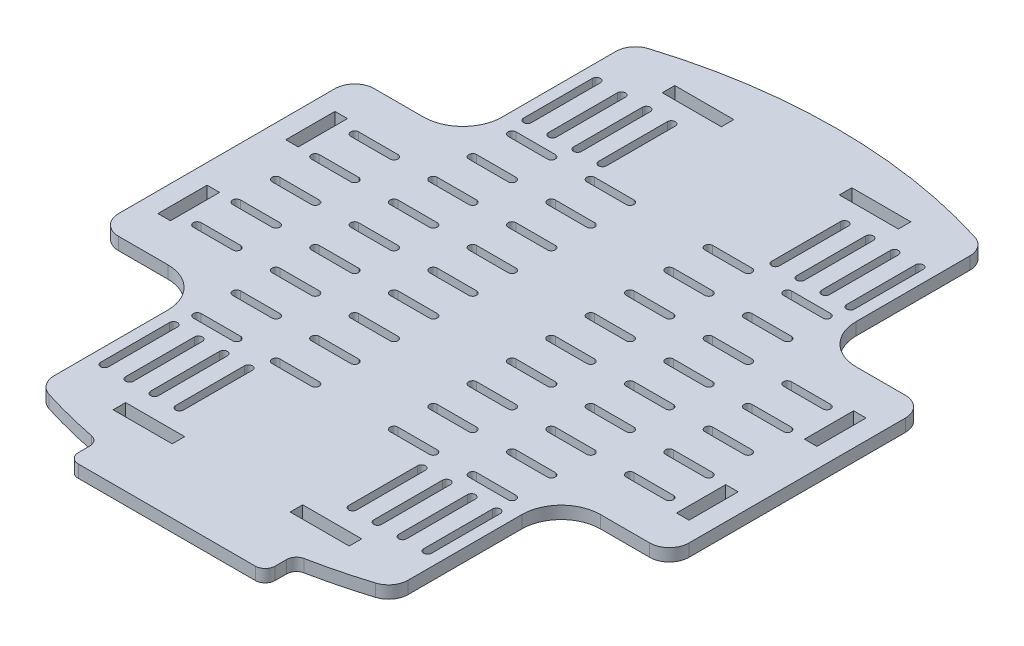
SolidWorks part; units mm, degrees
ref_plane "Plan de face" through (0, 0, 0) normal (0, 0, 1) x (1, 0, 0)
ref_plane "Plan de dessus" through (0, 0, 0) normal (0, 1, 0) x (1, 0, 0)
ref_plane "Plan de droite" through (0, 0, 0) normal (1, 0, 0) x (0, 0, -1)
sketch "Esquisse1" plane through (0, 0, 0) normal (0, 1, 0) x (1, 0, 0)
  line L0 (-145, 0) -> (0, 0) construction
  line L1 (-90, -150) -> (90, -150)
  line L2 (-90, -150) -> (-90, 150)
  line L3 (-90, 150) -> (90, 150)
  line L4 (90, -150) -> (90, 150)
  line L5 (-90, -150) -> (90, 150) construction
  line L6 (-90, 150) -> (90, -150) construction
  line L7 (-90, 65) -> (-145, 65)
  line L8 (-90, 65) -> (-90, -65)
  line L9 (-90, -65) -> (-145, -65)
  line L10 (-145, 65) -> (-145, -65)
  line L11 (0, 0) -> (0, -275) construction
  line L12 (90, -65) -> (145, -65)
  line L13 (145, 65) -> (145, -65)
  line L14 (90, 65) -> (145, 65)
  line L15 (90, 65) -> (90, -65)
  arc A0 (-90, 150) -> (90, 150) centre (0, -112.5) cw
  arc A1 (-90, -150) -> (90, -150) centre (0, 112.5) ccw
  point P0 (0, 0)
  point P19 (0, 165)
  point P20 (0, -165)
  dimension "D1" = 180
  dimension "D2" = 300
  dimension "D3" = 85
  dimension "D4" = 55
  dimension "D5" = 15
  dimension "D6" = 15
extrude "Boss.-Extru.1" add sketch "Esquisse1" along normal blind 6.35 contours L1 L4 L3 L2 | L7 L10 L9 L2 | L14 L4 L12 L13 | L1 A1 | A0 L3 region at (0, 0, 0) region at (0, 0, 156.0141) region at (-117.5, 0, 0) region at (117.5, 0, 0) region at (0, 0, -156.0141)
ref_plane "Plan1" through (0, 0, 150) normal (0, 0, -1) x (-1, 0, 0)
ref_plane "Plan3" through (0, 0, -150) normal (0, 0, -1) x (-1, 0, 0)
ref_plane "Wheel axis1" through (0, 0, 107.5) normal (0, 0, 1) x (1, 0, 0)
ref_plane "Wheel axis2" through (0, 0, -107.5) normal (0, 0, -1) x (-1, 0, 0)
sketch "Esquisse3" plane through (0, 6.35, 0) normal (0, 1, 0) x (1, 0, 0)
  line L0 (0, -160.4583) -> (0, 0) construction
  line L1 (-50, -160.4583) -> (50, -160.4583)
  line L2 (-50, -160.4583) -> (-50, -175.4583)
  line L3 (-50, -175.4583) -> (50, -175.4583)
  line L4 (50, -160.4583) -> (50, -175.4583)
  arc A0 (-90, -150) -> (90, -150) centre (0, 112.5) ccw construction
  dimension "D1" = 15
  dimension "D2" = 100
extrude "Boss.-Extru.2" add sketch "Esquisse3" against normal up to surface (6.35 mm away) up to face at (0, 0, 0)
sketch "Esquisse2" plane through (0, 0, 0) normal (0, -1, 0) x (1, 0, 0)
  line L0 (-128.65, 45) -> (-135, 45) construction
  line L1 (-135, 45) -> (-135, 20) construction
  line L2 (-135, 20) -> (-128.65, 20) construction
  line L3 (-128.65, 20) -> (-128.65, 45) construction
  line L4 (-128.65, -20) -> (-135, -20) construction
  line L5 (-135, -20) -> (-135, -45) construction
  line L6 (-135, -45) -> (-128.65, -45) construction
  line L7 (-128.65, -45) -> (-128.65, -20) construction
  line L8 (-60, -136.4072) -> (-60, -142.7572) construction
  line L9 (-60, -142.7572) -> (-30, -142.7572) construction
  line L10 (-30, -142.7572) -> (-30, -136.4072) construction
  line L11 (-30, -136.4072) -> (-60, -136.4072) construction
  line L12 (30, -136.4072) -> (30, -142.7572) construction
  line L13 (30, -142.7572) -> (60, -142.7572) construction
  line L14 (60, -142.7572) -> (60, -136.4072) construction
  line L15 (60, -136.4072) -> (30, -136.4072) construction
  line L16 (135, -20) -> (128.65, -20) construction
  line L17 (128.65, -20) -> (128.65, -45) construction
  line L18 (128.65, -45) -> (135, -45) construction
  line L19 (135, -45) -> (135, -20) construction
  line L20 (135, 45) -> (128.65, 45) construction
  line L21 (128.65, 45) -> (128.65, 20) construction
  line L22 (128.65, 20) -> (135, 20) construction
  line L23 (135, 20) -> (135, 45) construction
  line L24 (30, 142.7572) -> (30, 136.4072) construction
  line L25 (30, 136.4072) -> (60, 136.4072) construction
  line L26 (60, 136.4072) -> (60, 142.7572) construction
  line L27 (60, 142.7572) -> (30, 142.7572) construction
  line L28 (-60, 142.7572) -> (-60, 136.4072) construction
  line L29 (-60, 136.4072) -> (-30, 136.4072) construction
  line L30 (-30, 136.4072) -> (-30, 142.7572) construction
  line L31 (-30, 142.7572) -> (-60, 142.7572) construction
  line L32 (-128.65, 45) -> (-135, 45)
  line L33 (-135, 45) -> (-135, 20)
  line L34 (-135, 20) -> (-128.65, 20)
  line L35 (-128.65, 20) -> (-128.65, 45)
  line L36 (-128.65, -20) -> (-135, -20)
  line L37 (-135, -20) -> (-135, -45)
  line L38 (-135, -45) -> (-128.65, -45)
  line L39 (-128.65, -45) -> (-128.65, -20)
  line L40 (-60, -136.4072) -> (-60, -142.7572)
  line L41 (-60, -142.7572) -> (-30, -142.7572)
  line L42 (-30, -142.7572) -> (-30, -136.4072)
  line L43 (-30, -136.4072) -> (-60, -136.4072)
  line L44 (30, -136.4072) -> (30, -142.7572)
  line L45 (30, -142.7572) -> (60, -142.7572)
  line L46 (60, -142.7572) -> (60, -136.4072)
  line L47 (60, -136.4072) -> (30, -136.4072)
  line L48 (135, -20) -> (128.65, -20)
  line L49 (128.65, -20) -> (128.65, -45)
  line L50 (128.65, -45) -> (135, -45)
  line L51 (135, -45) -> (135, -20)
  line L52 (135, 45) -> (128.65, 45)
  line L53 (128.65, 45) -> (128.65, 20)
  line L54 (128.65, 20) -> (135, 20)
  line L55 (135, 20) -> (135, 45)
  line L56 (30, 142.7572) -> (30, 136.4072)
  line L57 (30, 136.4072) -> (60, 136.4072)
  line L58 (60, 136.4072) -> (60, 142.7572)
  line L59 (60, 142.7572) -> (30, 142.7572)
  line L60 (-60, 142.7572) -> (-60, 136.4072)
  line L61 (-60, 136.4072) -> (-30, 136.4072)
  line L62 (-30, 136.4072) -> (-30, 142.7572)
  line L63 (-30, 142.7572) -> (-60, 142.7572)
extrude "Enlèv. mat.-Extru.1" cut sketch "Esquisse2" against normal up to next
sketch "Esquisse4" plane through (0, 6.35, 0) normal (0, 1, 0) x (1, 0, 0)
  line L0 (-80, 0) -> (-60, 0) construction
  line L1 (-80, 2) -> (-60, 2)
  line L2 (-80, -2) -> (-60, -2)
  line L3 (-20, 0) -> (-40, 0) construction
  line L4 (-20, -2) -> (-40, -2)
  line L5 (-20, 2) -> (-40, 2)
  line L6 (30, 0) -> (-30, 0) construction
  line L7 (-30, 0) -> (-70, 0) construction
  line L8 (-80, 20) -> (-60, 20) construction
  line L9 (-80, 22) -> (-60, 22)
  line L10 (-80, 18) -> (-60, 18)
  line L11 (-20, 20) -> (-40, 20) construction
  line L12 (-20, 18) -> (-40, 18)
  line L13 (-20, 22) -> (-40, 22)
  line L14 (-80, 40) -> (-60, 40) construction
  line L15 (-80, 42) -> (-60, 42)
  line L16 (-80, 38) -> (-60, 38)
  line L17 (-20, 40) -> (-40, 40) construction
  line L18 (-20, 38) -> (-40, 38)
  line L19 (-20, 42) -> (-40, 42)
  line L20 (-80, 60) -> (-60, 60) construction
  line L21 (-80, 62) -> (-60, 62)
  line L22 (-80, 58) -> (-60, 58)
  line L23 (-20, 60) -> (-40, 60) construction
  line L24 (-20, 58) -> (-40, 58)
  line L25 (-20, 62) -> (-40, 62)
  line L26 (-80, -20) -> (-60, -20) construction
  line L27 (-80, -18) -> (-60, -18)
  line L28 (-80, -22) -> (-60, -22)
  line L29 (-20, -20) -> (-40, -20) construction
  line L30 (-20, -22) -> (-40, -22)
  line L31 (-20, -18) -> (-40, -18)
  line L32 (-80, -40) -> (-60, -40) construction
  line L33 (-80, -38) -> (-60, -38)
  line L34 (-80, -42) -> (-60, -42)
  line L35 (-20, -40) -> (-40, -40) construction
  line L36 (-20, -42) -> (-40, -42)
  line L37 (-20, -38) -> (-40, -38)
  line L38 (-80, -60) -> (-60, -60) construction
  line L39 (-80, -58) -> (-60, -58)
  line L40 (-80, -62) -> (-60, -62)
  line L41 (-20, -60) -> (-40, -60) construction
  line L42 (-20, -62) -> (-40, -62)
  line L43 (-20, -58) -> (-40, -58)
  line L44 (-80, -80) -> (-60, -80) construction
  line L45 (-80, -78) -> (-60, -78)
  line L46 (-80, -82) -> (-60, -82)
  line L47 (-20, -80) -> (-40, -80) construction
  line L48 (-20, -82) -> (-40, -82)
  line L49 (-20, -78) -> (-40, -78)
  line L50 (-120, 0) -> (-100, 0) construction
  line L53 (-120, 2) -> (-100, 2)
  line L56 (-120, -2) -> (-100, -2)
  line L59 (-120, 20) -> (-100, 20) construction
  line L62 (-80, 80) -> (-60, 80) construction
  line L63 (-80, 82) -> (-60, 82)
  line L64 (-80, 78) -> (-60, 78)
  line L65 (-20, 80) -> (-40, 80) construction
  line L66 (-20, 78) -> (-40, 78)
  line L67 (-20, 82) -> (-40, 82)
  line L68 (-120, 22) -> (-100, 22)
  line L71 (-120, 18) -> (-100, 18)
  line L74 (-120, 40) -> (-100, 40) construction
  line L77 (-120, 42) -> (-100, 42)
  line L80 (0, 0) -> (0, -28.7119) construction
  line L81 (80, 0) -> (60, 0) construction
  line L82 (80, 2) -> (60, 2)
  line L83 (80, -2) -> (60, -2)
  line L84 (20, 0) -> (40, 0) construction
  line L85 (20, -2) -> (40, -2)
  line L86 (20, 2) -> (40, 2)
  line L87 (80, 20) -> (60, 20) construction
  line L88 (80, 22) -> (60, 22)
  line L89 (80, 18) -> (60, 18)
  line L90 (20, 20) -> (40, 20) construction
  line L91 (20, 18) -> (40, 18)
  line L92 (20, 22) -> (40, 22)
  line L93 (80, 40) -> (60, 40) construction
  line L94 (80, 42) -> (60, 42)
  line L95 (80, 38) -> (60, 38)
  line L96 (20, 40) -> (40, 40) construction
  line L97 (20, 38) -> (40, 38)
  line L98 (20, 42) -> (40, 42)
  line L99 (80, 60) -> (60, 60) construction
  line L100 (80, 62) -> (60, 62)
  line L101 (80, 58) -> (60, 58)
  line L102 (20, 60) -> (40, 60) construction
  line L103 (20, 58) -> (40, 58)
  line L104 (20, 62) -> (40, 62)
  line L105 (80, -20) -> (60, -20) construction
  line L106 (80, -18) -> (60, -18)
  line L107 (80, -22) -> (60, -22)
  line L108 (20, -20) -> (40, -20) construction
  line L109 (20, -22) -> (40, -22)
  line L110 (20, -18) -> (40, -18)
  line L111 (80, -40) -> (60, -40) construction
  line L112 (80, -38) -> (60, -38)
  line L113 (80, -42) -> (60, -42)
  line L114 (20, -40) -> (40, -40) construction
  line L115 (20, -42) -> (40, -42)
  line L116 (20, -38) -> (40, -38)
  line L117 (80, -60) -> (60, -60) construction
  line L118 (80, -58) -> (60, -58)
  line L119 (80, -62) -> (60, -62)
  line L120 (20, -60) -> (40, -60) construction
  line L121 (20, -62) -> (40, -62)
  line L122 (20, -58) -> (40, -58)
  line L123 (80, -80) -> (60, -80) construction
  line L124 (80, -78) -> (60, -78)
  line L125 (80, -82) -> (60, -82)
  line L126 (20, -80) -> (40, -80) construction
  line L127 (20, -82) -> (40, -82)
  line L128 (20, -78) -> (40, -78)
  line L129 (-120, 38) -> (-100, 38)
  line L132 (-120, -20) -> (-100, -20) construction
  line L135 (-120, -18) -> (-100, -18)
  line L138 (-120, -22) -> (-100, -22)
  line L141 (80, 80) -> (60, 80) construction
  line L142 (80, 82) -> (60, 82)
  line L143 (80, 78) -> (60, 78)
  line L144 (20, 80) -> (40, 80) construction
  line L145 (20, 78) -> (40, 78)
  line L146 (20, 82) -> (40, 82)
  line L147 (-120, -40) -> (-100, -40) construction
  line L150 (-120, -38) -> (-100, -38)
  line L153 (-120, -42) -> (-100, -42)
  line L156 (120, 0) -> (100, 0) construction
  line L159 (30, 0) -> (70, 0) construction
  line L160 (120, 2) -> (100, 2)
  line L161 (120, -2) -> (100, -2)
  line L162 (120, 20) -> (100, 20) construction
  line L163 (120, 22) -> (100, 22)
  line L164 (120, 18) -> (100, 18)
  line L165 (120, 40) -> (100, 40) construction
  line L166 (120, 42) -> (100, 42)
  line L167 (120, 38) -> (100, 38)
  line L168 (120, -20) -> (100, -20) construction
  line L169 (120, -18) -> (100, -18)
  line L170 (120, -22) -> (100, -22)
  line L171 (120, -40) -> (100, -40) construction
  line L172 (120, -38) -> (100, -38)
  line L173 (120, -42) -> (100, -42)
  arc A0 (-80, 2) -> (-80, -2) centre (-80, 0) ccw
  arc A1 (-60, -2) -> (-60, 2) centre (-60, 0) ccw
  arc A2 (-20, -2) -> (-20, 2) centre (-20, 0) ccw
  arc A3 (-40, 2) -> (-40, -2) centre (-40, 0) ccw
  arc A4 (-80, 22) -> (-80, 18) centre (-80, 20) ccw
  arc A5 (-60, 18) -> (-60, 22) centre (-60, 20) ccw
  arc A6 (-20, 18) -> (-20, 22) centre (-20, 20) ccw
  arc A7 (-40, 22) -> (-40, 18) centre (-40, 20) ccw
  arc A8 (-80, 42) -> (-80, 38) centre (-80, 40) ccw
  arc A9 (-60, 38) -> (-60, 42) centre (-60, 40) ccw
  arc A10 (-20, 38) -> (-20, 42) centre (-20, 40) ccw
  arc A11 (-40, 42) -> (-40, 38) centre (-40, 40) ccw
  arc A12 (-80, 62) -> (-80, 58) centre (-80, 60) ccw
  arc A13 (-60, 58) -> (-60, 62) centre (-60, 60) ccw
  arc A14 (-20, 58) -> (-20, 62) centre (-20, 60) ccw
  arc A15 (-40, 62) -> (-40, 58) centre (-40, 60) ccw
  arc A16 (-80, -18) -> (-80, -22) centre (-80, -20) ccw
  arc A17 (-60, -22) -> (-60, -18) centre (-60, -20) ccw
  arc A18 (-20, -22) -> (-20, -18) centre (-20, -20) ccw
  arc A19 (-40, -18) -> (-40, -22) centre (-40, -20) ccw
  arc A20 (-80, -38) -> (-80, -42) centre (-80, -40) ccw
  arc A21 (-60, -42) -> (-60, -38) centre (-60, -40) ccw
  arc A22 (-20, -42) -> (-20, -38) centre (-20, -40) ccw
  arc A23 (-40, -38) -> (-40, -42) centre (-40, -40) ccw
  arc A24 (-80, -58) -> (-80, -62) centre (-80, -60) ccw
  arc A25 (-60, -62) -> (-60, -58) centre (-60, -60) ccw
  arc A26 (-20, -62) -> (-20, -58) centre (-20, -60) ccw
  arc A27 (-40, -58) -> (-40, -62) centre (-40, -60) ccw
  arc A28 (-80, -78) -> (-80, -82) centre (-80, -80) ccw
  arc A29 (-60, -82) -> (-60, -78) centre (-60, -80) ccw
  arc A30 (-20, -82) -> (-20, -78) centre (-20, -80) ccw
  arc A31 (-40, -78) -> (-40, -82) centre (-40, -80) ccw
  arc A40 (-80, 82) -> (-80, 78) centre (-80, 80) ccw
  arc A41 (-60, 78) -> (-60, 82) centre (-60, 80) ccw
  arc A42 (-20, 78) -> (-20, 82) centre (-20, 80) ccw
  arc A43 (-40, 82) -> (-40, 78) centre (-40, 80) ccw
  arc A52 (80, 2) -> (80, -2) centre (80, 0) cw
  arc A53 (60, -2) -> (60, 2) centre (60, 0) cw
  arc A54 (20, -2) -> (20, 2) centre (20, 0) cw
  arc A55 (40, 2) -> (40, -2) centre (40, 0) cw
  arc A56 (80, 22) -> (80, 18) centre (80, 20) cw
  arc A57 (60, 18) -> (60, 22) centre (60, 20) cw
  arc A58 (20, 18) -> (20, 22) centre (20, 20) cw
  arc A59 (40, 22) -> (40, 18) centre (40, 20) cw
  arc A60 (80, 42) -> (80, 38) centre (80, 40) cw
  arc A61 (60, 38) -> (60, 42) centre (60, 40) cw
  arc A62 (20, 38) -> (20, 42) centre (20, 40) cw
  arc A63 (40, 42) -> (40, 38) centre (40, 40) cw
  arc A64 (80, 62) -> (80, 58) centre (80, 60) cw
  arc A65 (60, 58) -> (60, 62) centre (60, 60) cw
  arc A66 (20, 58) -> (20, 62) centre (20, 60) cw
  arc A67 (40, 62) -> (40, 58) centre (40, 60) cw
  arc A68 (80, -18) -> (80, -22) centre (80, -20) cw
  arc A69 (60, -22) -> (60, -18) centre (60, -20) cw
  arc A70 (20, -22) -> (20, -18) centre (20, -20) cw
  arc A71 (40, -18) -> (40, -22) centre (40, -20) cw
  arc A72 (80, -38) -> (80, -42) centre (80, -40) cw
  arc A73 (60, -42) -> (60, -38) centre (60, -40) cw
  arc A74 (20, -42) -> (20, -38) centre (20, -40) cw
  arc A75 (40, -38) -> (40, -42) centre (40, -40) cw
  arc A76 (80, -58) -> (80, -62) centre (80, -60) cw
  arc A77 (60, -62) -> (60, -58) centre (60, -60) cw
  arc A78 (20, -62) -> (20, -58) centre (20, -60) cw
  arc A79 (40, -58) -> (40, -62) centre (40, -60) cw
  arc A80 (80, -78) -> (80, -82) centre (80, -80) cw
  arc A81 (60, -82) -> (60, -78) centre (60, -80) cw
  arc A82 (20, -82) -> (20, -78) centre (20, -80) cw
  arc A83 (40, -78) -> (40, -82) centre (40, -80) cw
  arc A92 (80, 82) -> (80, 78) centre (80, 80) cw
  arc A93 (60, 78) -> (60, 82) centre (60, 80) cw
  arc A94 (20, 78) -> (20, 82) centre (20, 80) cw
  arc A95 (40, 82) -> (40, 78) centre (40, 80) cw
  arc A104 (-120, 2) -> (-120, -2) centre (-120, 0) ccw
  arc A105 (-100, -2) -> (-100, 2) centre (-100, 0) ccw
  arc A106 (-120, 22) -> (-120, 18) centre (-120, 20) ccw
  arc A107 (-100, 18) -> (-100, 22) centre (-100, 20) ccw
  arc A108 (-120, 42) -> (-120, 38) centre (-120, 40) ccw
  arc A109 (-100, 38) -> (-100, 42) centre (-100, 40) ccw
  arc A110 (-120, -18) -> (-120, -22) centre (-120, -20) ccw
  arc A111 (-100, -22) -> (-100, -18) centre (-100, -20) ccw
  arc A112 (-120, -38) -> (-120, -42) centre (-120, -40) ccw
  arc A113 (-100, -42) -> (-100, -38) centre (-100, -40) ccw
  arc A114 (120, 2) -> (120, -2) centre (120, 0) cw
  arc A115 (100, -2) -> (100, 2) centre (100, 0) cw
  arc A116 (120, 22) -> (120, 18) centre (120, 20) cw
  arc A117 (100, 18) -> (100, 22) centre (100, 20) cw
  arc A118 (120, 42) -> (120, 38) centre (120, 40) cw
  arc A119 (100, 38) -> (100, 42) centre (100, 40) cw
  arc A120 (120, -18) -> (120, -22) centre (120, -20) cw
  arc A121 (100, -22) -> (100, -18) centre (100, -20) cw
  arc A122 (120, -38) -> (120, -42) centre (120, -40) cw
  arc A123 (100, -42) -> (100, -38) centre (100, -40) cw
  point P3 (-70, 0)
  point P8 (-30, 0)
  point P22 (-70, 20)
  point P27 (-30, 20)
  point P36 (-70, 40)
  point P41 (-30, 40)
  point P50 (-70, 60)
  point P55 (-30, 60)
  point P63 (-70, -20)
  point P68 (-30, -20)
  point P77 (-70, -40)
  point P82 (-30, -40)
  point P91 (-70, -60)
  point P96 (-30, -60)
  point P105 (-70, -80)
  point P110 (-30, -80)
  point P120 (-110, 0)
  point P129 (-110, 20)
  point P136 (-110, 40)
  point P141 (-110, -20)
  point P146 (-70, 80)
  point P151 (-30, 80)
  point P161 (-110, -40)
  point P167 (110, 0)
  point P174 (110, 20)
  point P181 (110, 40)
  point P189 (70, 0)
  point P196 (30, 0)
  point P203 (70, 20)
  point P210 (30, 20)
  point P217 (70, 40)
  point P224 (30, 40)
  point P231 (70, 60)
  point P238 (30, 60)
  point P245 (70, -20)
  point P252 (30, -20)
  point P259 (70, -40)
  point P266 (30, -40)
  point P273 (70, -60)
  point P280 (30, -60)
  point P287 (70, -80)
  point P294 (30, -80)
  point P301 (110, -20)
  point P308 (110, -40)
  point P329 (70, 80)
  point P336 (30, 80)
  dimension "D1" = 30
  dimension "D2" = 20
  dimension "D3" = 4
  dimension "D5" = 20
  dimension "D7" = 40
  dimension "D8" = 20
  dimension "D10" = 40
  dimension "D4" = 5
  dimension "D6" = 5
  dimension "D9" = 2
extrude "Enlèv. mat.-Extru.2" cut sketch "Esquisse4" against normal up to next (6.35 mm away)
sketch "Esquisse5" plane through (0, 6.35, 0) normal (0, 1, 0) x (1, 0, 0)
  line L0 (-82.1, 125) -> (-82.1, 90) construction
  line L1 (-80.1, 125) -> (-80.1, 90)
  line L2 (-84.1, 125) -> (-84.1, 90)
  line L4 (3.4925, 107.5) -> (-3.4925, 107.5) construction
  line L5 (-82.1, 107.5) -> (-90, 107.5) construction
  line L6 (-69.4, 125) -> (-69.4, 90) construction
  line L7 (-67.4, 125) -> (-67.4, 90)
  line L8 (-71.4, 125) -> (-71.4, 90)
  line L9 (-56.7, 125) -> (-56.7, 90) construction
  line L10 (-54.7, 125) -> (-54.7, 90)
  line L11 (-58.7, 125) -> (-58.7, 90)
  line L12 (-44, 125) -> (-44, 90) construction
  line L13 (-42, 125) -> (-42, 90)
  line L14 (-46, 125) -> (-46, 90)
  line L15 (0, 0) -> (0, 28.4407) construction
  line L16 (0, 0) -> (-12.927, 0) construction
  line L17 (82.1, 125) -> (82.1, 90) construction
  line L18 (80.1, 125) -> (80.1, 90)
  line L19 (84.1, 125) -> (84.1, 90)
  line L20 (69.4, 125) -> (69.4, 90) construction
  line L21 (67.4, 125) -> (67.4, 90)
  line L22 (71.4, 125) -> (71.4, 90)
  line L23 (56.7, 125) -> (56.7, 90) construction
  line L24 (54.7, 125) -> (54.7, 90)
  line L25 (58.7, 125) -> (58.7, 90)
  line L26 (44, 125) -> (44, 90) construction
  line L27 (42, 125) -> (42, 90)
  line L28 (46, 125) -> (46, 90)
  line L29 (-82.1, -125) -> (-82.1, -90) construction
  line L30 (-80.1, -125) -> (-80.1, -90)
  line L31 (-84.1, -125) -> (-84.1, -90)
  line L32 (-69.4, -125) -> (-69.4, -90) construction
  line L33 (-67.4, -125) -> (-67.4, -90)
  line L34 (-71.4, -125) -> (-71.4, -90)
  line L35 (-56.7, -125) -> (-56.7, -90) construction
  line L36 (-54.7, -125) -> (-54.7, -90)
  line L37 (-58.7, -125) -> (-58.7, -90)
  line L38 (-44, -125) -> (-44, -90) construction
  line L39 (-42, -125) -> (-42, -90)
  line L40 (-46, -125) -> (-46, -90)
  line L41 (82.1, -125) -> (82.1, -90) construction
  line L42 (80.1, -125) -> (80.1, -90)
  line L43 (84.1, -125) -> (84.1, -90)
  line L44 (69.4, -125) -> (69.4, -90) construction
  line L45 (67.4, -125) -> (67.4, -90)
  line L46 (71.4, -125) -> (71.4, -90)
  line L47 (56.7, -125) -> (56.7, -90) construction
  line L48 (54.7, -125) -> (54.7, -90)
  line L49 (58.7, -125) -> (58.7, -90)
  line L50 (44, -125) -> (44, -90) construction
  line L51 (42, -125) -> (42, -90)
  line L52 (46, -125) -> (46, -90)
  line L53 (-82.1, -107.5) -> (-90, -107.5) construction
  line L54 (-90, 65) -> (-90, 150) construction
  arc A0 (-80.1, 125) -> (-84.1, 125) centre (-82.1, 125) ccw
  arc A1 (-84.1, 90) -> (-80.1, 90) centre (-82.1, 90) ccw
  arc A2 (-67.4, 125) -> (-71.4, 125) centre (-69.4, 125) ccw
  arc A3 (-71.4, 90) -> (-67.4, 90) centre (-69.4, 90) ccw
  arc A4 (-54.7, 125) -> (-58.7, 125) centre (-56.7, 125) ccw
  arc A5 (-58.7, 90) -> (-54.7, 90) centre (-56.7, 90) ccw
  arc A6 (-42, 125) -> (-46, 125) centre (-44, 125) ccw
  arc A7 (-46, 90) -> (-42, 90) centre (-44, 90) ccw
  arc A8 (80.1, 125) -> (84.1, 125) centre (82.1, 125) cw
  arc A9 (84.1, 90) -> (80.1, 90) centre (82.1, 90) cw
  arc A10 (67.4, 125) -> (71.4, 125) centre (69.4, 125) cw
  arc A11 (71.4, 90) -> (67.4, 90) centre (69.4, 90) cw
  arc A12 (54.7, 125) -> (58.7, 125) centre (56.7, 125) cw
  arc A13 (58.7, 90) -> (54.7, 90) centre (56.7, 90) cw
  arc A14 (42, 125) -> (46, 125) centre (44, 125) cw
  arc A15 (46, 90) -> (42, 90) centre (44, 90) cw
  arc A16 (-80.1, -125) -> (-84.1, -125) centre (-82.1, -125) cw
  arc A17 (-84.1, -90) -> (-80.1, -90) centre (-82.1, -90) cw
  arc A18 (-67.4, -125) -> (-71.4, -125) centre (-69.4, -125) cw
  arc A19 (-71.4, -90) -> (-67.4, -90) centre (-69.4, -90) cw
  arc A20 (-54.7, -125) -> (-58.7, -125) centre (-56.7, -125) cw
  arc A21 (-58.7, -90) -> (-54.7, -90) centre (-56.7, -90) cw
  arc A22 (-42, -125) -> (-46, -125) centre (-44, -125) cw
  arc A23 (-46, -90) -> (-42, -90) centre (-44, -90) cw
  arc A24 (80.1, -125) -> (84.1, -125) centre (82.1, -125) ccw
  arc A25 (84.1, -90) -> (80.1, -90) centre (82.1, -90) ccw
  arc A26 (67.4, -125) -> (71.4, -125) centre (69.4, -125) ccw
  arc A27 (71.4, -90) -> (67.4, -90) centre (69.4, -90) ccw
  arc A28 (54.7, -125) -> (58.7, -125) centre (56.7, -125) ccw
  arc A29 (58.7, -90) -> (54.7, -90) centre (56.7, -90) ccw
  arc A30 (42, -125) -> (46, -125) centre (44, -125) ccw
  arc A31 (46, -90) -> (42, -90) centre (44, -90) ccw
  point P2 (-82.1, 107.5)
  point P7 (-90, 107.5)
  point P9 (-90, 107.5)
  point P17 (-69.4, 107.5)
  point P24 (-56.7, 107.5)
  point P31 (-44, 107.5)
  point P41 (82.1, 107.5)
  point P48 (69.4, 107.5)
  point P55 (56.7, 107.5)
  point P62 (44, 107.5)
  point P69 (-82.1, -107.5)
  point P76 (-69.4, -107.5)
  point P83 (-56.7, -107.5)
  point P90 (-44, -107.5)
  point P97 (82.1, -107.5)
  point P104 (69.4, -107.5)
  point P111 (56.7, -107.5)
  point P118 (44, -107.5)
  point P125 (-90, -107.5)
  point P126 (0, 0)
  point P128 (-90, 88.3273)
  dimension "D1" = 4
  dimension "D2" = 7.9
  dimension "D3" = 35
  dimension "D4" = 4
  dimension "D5" = 12.7
extrude "Enlèv. mat.-Extru.3" cut sketch "Esquisse5" against normal up to next
fillet "Congé1" radius 20 4 edges at (90, 3.175, -65) (-90, 3.175, -65) (-90, 3.175, 65) (90, 3.175, 65)
fillet "Congé2" radius 10 8 edges at (-90, 3.175, -150) (-145, 3.175, -65) (-145, 3.175, 65) (-90, 3.175, 150) (90, 3.175, -150) (145, 3.175, -65) (145, 3.175, 65) (90, 3.175, 150)
fillet "Congé3" radius 5 4 edges at (-50, 3.175, 160.4583) (-50, 3.175, 175.4583) (50, 3.175, 175.4583) (50, 3.175, 160.4583)
